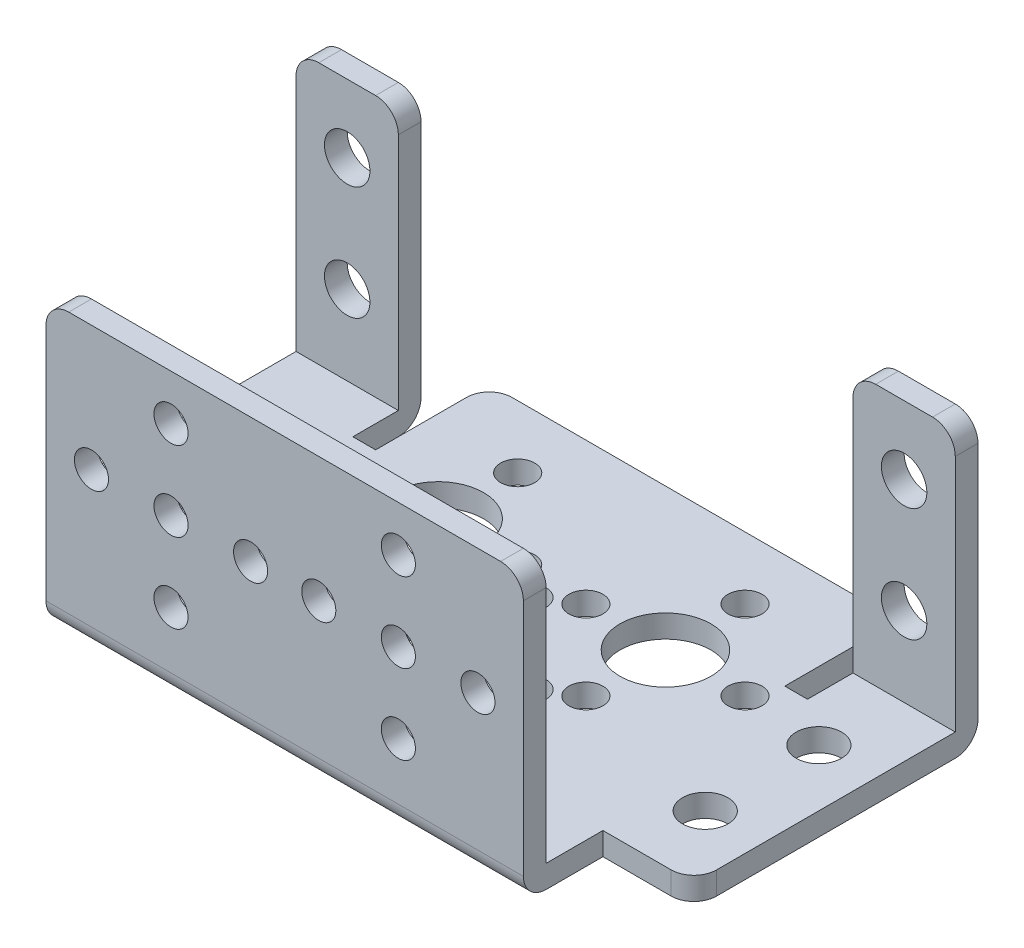
SolidWorks part; units mm, degrees
ref_plane "Front Plane" through (0, 0, 0) normal (0, 0, 1) x (1, 0, 0)
ref_plane "Top Plane" through (0, 0, 0) normal (0, 1, 0) x (1, 0, 0)
ref_plane "Right Plane" through (0, 0, 0) normal (1, 0, 0) x (0, 0, -1)
sketch "Sketch1" plane through (0, 0, 0) normal (0, 0, 1) x (1, 0, 0)
  line L1 (0, 0) -> (42, 0)
  line L2 (0, 0) -> (0, 25)
  line L3 (0, 25) -> (42, 25)
  line L4 (42, 0) -> (42, 25)
  circle A0 centre (11, 14) radius 1.5
  circle A1 centre (11, 21) radius 1.5
  circle A2 centre (18, 14) radius 1.5
  circle A3 centre (4, 14) radius 1.5
  circle A4 centre (11, 7) radius 1.5
  circle A5 centre (31, 14) radius 1.5
  circle A6 centre (38, 14) radius 1.5
  circle A7 centre (31, 21) radius 1.5
  circle A8 centre (24, 14) radius 1.5
  circle A9 centre (31, 7) radius 1.5
  dimension "D3" = 3
  dimension "D1" = 42
  dimension "D2" = 25
  dimension "D4" = 7
  dimension "D5" = 7
  dimension "D6" = 7
  dimension "D7" = 7
  dimension "D8" = 7
  dimension "D9" = 7
  dimension "D10" = 14
  dimension "D11" = 11
  dimension "D12" = 11
extrude "Boss-Extrude1" add sketch "Sketch1" against normal blind 2
sketch "Sketch2" plane through (0, 0, 0) normal (0, -1, 0) x (1, 0, 0)
  line L0 (0, -32) -> (0, -36)
  line L1 (0, 0) -> (42, 0)
  line L2 (0, 0) -> (0, -7)
  line L3 (0, -36) -> (42, -36)
  line L4 (42, 0) -> (42, -7)
  line L5 (-6, -7) -> (0, -7)
  line L6 (-8, -9) -> (-8, -32)
  line L7 (-8, -32) -> (0, -32)
  line L8 (50, -9) -> (50, -32)
  line L9 (42, -7) -> (48, -7)
  line L10 (42, -32) -> (50, -32)
  line L11 (42, -32) -> (42, -36)
  line L12 (21, -2) -> (21, -36) construction
  line L13 (0, -2) -> (42, -2) construction
  line L14 (19.5, -23.5) -> (21, -23.5) construction
  line L15 (22.5, -23.5) -> (21, -23.5) construction
  circle A0 centre (45, -13) radius 2
  circle A1 centre (45, -23) radius 2
  circle A2 centre (-3, -13) radius 2
  circle A3 centre (-3, -23) radius 2
  arc A4 (-6, -7) -> (-8, -9) centre (-6, -9) ccw
  arc A5 (48, -7) -> (50, -9) centre (48, -9) cw
  circle A6 centre (11, -23.5) radius 4
  circle A7 centre (31, -23.5) radius 4
  circle A8 centre (21, -14.5) radius 4
  circle A9 centre (11, -16.5) radius 1.5
  circle A10 centre (11, -30.5) radius 1.5
  circle A11 centre (18, -23.5) radius 1.5
  circle A12 centre (4, -23.5) radius 1.5
  circle A13 centre (31, -30.5) radius 1.5
  circle A14 centre (24, -23.5) radius 1.5
  circle A15 centre (31, -16.5) radius 1.5
  circle A16 centre (38, -23.5) radius 1.5
  circle A17 centre (21, -21.5) radius 1.5
  circle A18 centre (21, -7.5) radius 1.5
  circle A19 centre (28, -14.5) radius 1.5
  circle A20 centre (14, -14.5) radius 1.5
  point P24 (-8, -7)
  point P27 (50, -7)
  dimension "D6" = 2
  dimension "D7" = 4
  dimension "D8" = 10
  dimension "D10" = 5
  dimension "D11" = 5
  dimension "D12" = 8
  dimension "D13" = 14.5
  dimension "D14" = 12.5
  dimension "D15" = 3
  dimension "D1" = 36
  dimension "D2" = 25
  dimension "D3" = 7
  dimension "D4" = 58
  dimension "D5" = 8
  dimension "D9" = 6
  dimension "D16" = 7
  dimension "D17" = 7
  dimension "D18" = 7
  dimension "D19" = 7
  dimension "D20" = 7
  dimension "D21" = 7
  dimension "D22" = 7
  dimension "D23" = 7
  dimension "D24" = 7
  dimension "D25" = 7
  dimension "D26" = 20
  dimension "D27" = 7
extrude "Boss-Extrude2" add sketch "Sketch2" against normal blind 2
sketch "Sketch3" plane through (0, 0, 0) normal (0, -1, 0) x (1, 0, 0)
  line L0 (39, -36) -> (39, -26)
  line L1 (0, -36) -> (42, -36) construction
  line L2 (39, -26) -> (41, -26)
  line L3 (41, -26) -> (41, -32)
  line L4 (41, -32) -> (42, -32)
  line L17 (42, 0) -> (0, 0)
  line L18 (0, 0) -> (0, -7)
  line L19 (0, -7) -> (-6, -7)
  line L20 (-8, -9) -> (-8, -32)
  line L21 (-8, -32) -> (0, -32)
  line L22 (0, -32) -> (0, -36)
  line L23 (0, -36) -> (42, -36)
  line L24 (42, -36) -> (42, -32)
  line L25 (42, -32) -> (50, -32)
  line L26 (50, -32) -> (50, -9)
  line L27 (48, -7) -> (42, -7)
  line L28 (42, -7) -> (42, 0)
  line L35 (39, -36) -> (42, -36)
  line L36 (42, -36) -> (42, -32)
  arc A2 (-6, -7) -> (-8, -9) centre (-6, -9) ccw
  arc A3 (50, -9) -> (48, -7) centre (48, -9) ccw
  dimension "D1" = 10
  dimension "D2" = 2
  dimension "D3" = 1
  dimension "D4" = 0
extrude "Cut-Extrude1" cut sketch "Sketch3" against normal blind 2
ref_plane "Plane1" through (21, 0, 0) normal (1, 0, 0) x (0, 0, -1)
mirror "Mirror1" about plane through (21, 0, 0) normal (1, 0, 0) of "Cut-Extrude1"
fillet "Fillet1" radius 2 1 edges at (3, 1, -36)
fillet "Fillet2" radius 2 1 edges at (39, 1, -36)
fillet "Fillet3" radius 2 1 edges at (21, 0, 0)
fillet "Fillet4" radius 2 1 edges at (42, 25, -1)
fillet "Fillet5" radius 2 1 edges at (0, 25, -1)
sketch "Sketch4" plane through (0, 0, -32) normal (0, 0, -1) x (-1, 0, 0)
  line L1 (8, 0) -> (-1, 0)
  line L2 (8, 0) -> (8, 23)
  line L3 (6, 25) -> (1, 25)
  line L4 (-1, 0) -> (-1, 23)
  arc A0 (8, 23) -> (6, 25) centre (6, 23) ccw
  arc A1 (1, 25) -> (-1, 23) centre (1, 23) ccw
  dimension "D1" = 2
  dimension "D2" = 9
  dimension "D3" = 25
extrude "Boss-Extrude3" add sketch "Sketch4" against normal blind 2
mirror "Mirror2" about plane through (21, 0, 0) normal (1, 0, 0) of "Boss-Extrude3"
fillet "Fillet6" radius 2 1 edges at (45.5, 0, -32)
fillet "Fillet7" radius 2 1 edges at (-3.5, 0, -32)
sketch "Sketch5" plane through (0, 0, -32) normal (0, 0, -1) x (-1, 0, 0)
  line L0 (3.5, 25) -> (3.5, 0) construction
  line L1 (6, 25) -> (1, 25) construction
  circle A0 centre (3.5, 19) radius 2
  circle A1 centre (3.5, 9) radius 2
  dimension "D2" = 4
  dimension "D1" = 10
  dimension "D3" = 6
extrude "Cut-Extrude2" cut sketch "Sketch5" against normal blind 2
mirror "Mirror3" about plane through (21, 0, 0) normal (1, 0, 0) of "Cut-Extrude2"
